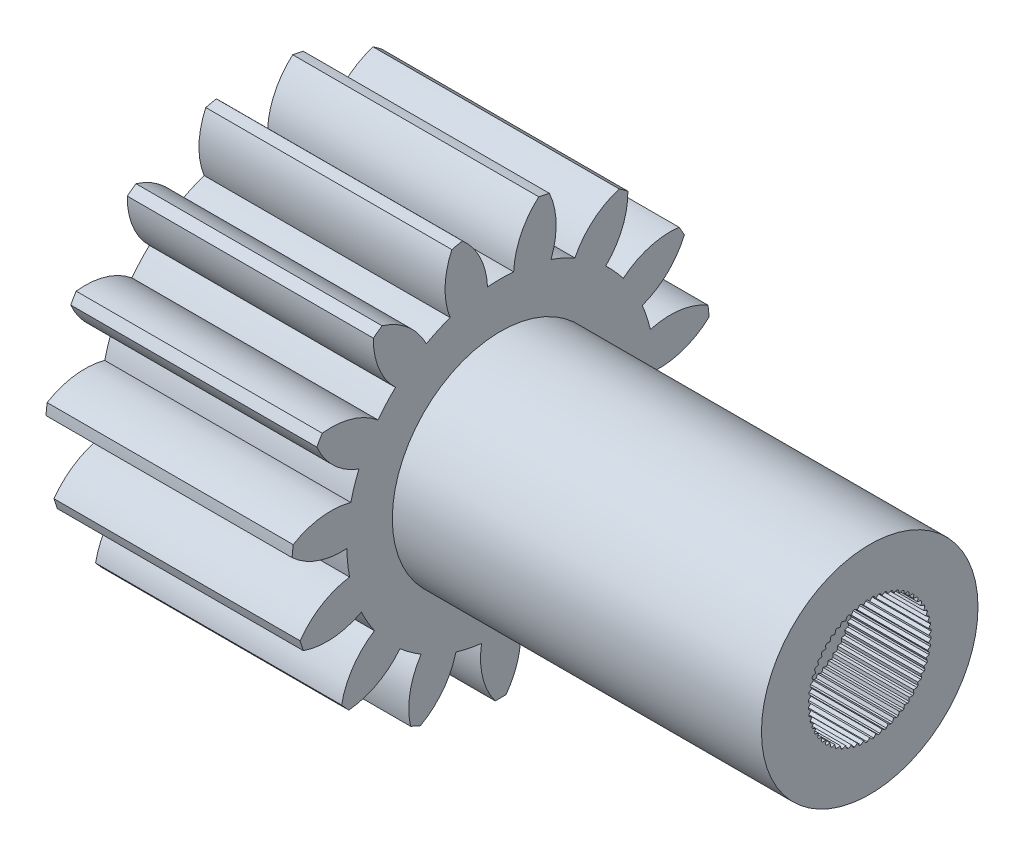
SolidWorks part; units mm, degrees
ref_plane "Plane1" through (0, 0, 0) normal (0, 0, 1) x (1, 0, 0)
ref_plane "Plane2" through (0, 0, 0) normal (0, 1, 0) x (1, 0, 0)
ref_plane "Plane3" through (0, 0, 0) normal (1, 0, 0) x (0, 0, -1)
sketch "HoldingSke" plane through (0, 0, 0) normal (0, 1, 0) x (1, 0, 0)
  line L0 (0, 0) -> (0.9659, -0.2588)
  line L1 (-15, 0) -> (100, 0) construction
  line L2 (0, 0) -> (-2.1039, 2.3779)
  line L3 (0, 0) -> (-11.863, 4.5341)
  line L4 (0, 0) -> (8.3417, 2.2352)
  line L5 (0, 0) -> (-46.8476, -17.4728)
  line L6 (0, 0) -> (-8.2896, -5.593)
  line L7 (-2.1039, 2.3779) -> (8.6586, 51.2059)
  line L8 (-76.2, 54.61) -> (-75.3, 54.61)
  line L9 (-71.009, 38.7566) -> (-53.1078, 45.2721)
  line L10 (-76.2, 71.12) -> (104.1128, 71.12)
  line L11 (0, 0) -> (-10, 0)
  line L12 (-76.2, 101.6) -> (-76.162, 101.6)
  line L13 (24.9733, 27.94) -> (52.9518, 28.4284)
  line L14 (24.9733, 27.94) -> (24.9743, 27.94)
  line L15 (24.9733, 27.94) -> (100.4006, 29.5858)
  line L16 (-63.627, -1) -> (-12.827, -1)
  circle A0 centre (0, 0) radius 2.5
  circle A1 centre (0, 0) radius 6.249
  circle A2 centre (0, 0) radius 37.5
  circle A3 centre (0, 0) radius 2.5
  dimension "Num_teeth" = 15
  dimension "Pitch_radius" = 180.3128
  dimension "Width" = 10
  dimension "Thickness" = 10
sketch "BasProSke" plane through (0, 0, 0) normal (0, 1, 0) x (1, 0, 0)
  line L0 (-10, 0) -> (60, 0) construction
  line L1 (0, 0) -> (0, 8.5)
  line L2 (0, 0) -> (10, 0)
  line L3 (10, 0) -> (10, 8.5)
  line L4 (10, 8.5) -> (0, 8.5)
  dimension "Thickness" = 10
  dimension "Diameter" = 17
revolve "Base-Revolve" add sketch "BasProSke" angle 360 about L0
sketch "TooCutSke" plane through (0, 0, 0) normal (1, 0, 0) x (0, 0, -1)
  line L1 (0, 0) -> (0, 107) construction
  line L2 (0, 0) -> (-0.8504, 7.4516) construction
  line L3 (0, 0) -> (-3.1044, 14.6049) construction
  line L4 (-0.8504, 7.4516) -> (-1.5522, 7.3025) construction
  arc A0 (0.5316, 6.2263) -> (-0.5316, 6.2263) centre (0, 0) ccw
  arc A1 (1.5766, 8.3784) -> (-1.5766, 8.3784) centre (0, 0) ccw
  circle A2 centre (0, 0) radius 7.5 construction
  circle A3 centre (0, 0) radius 7.0477 construction
  arc A4 (-0.5316, 6.2263) -> (-1.5766, 8.3784) centre (-3.5289, 6.1005) ccw
  arc A5 (1.5766, 8.3784) -> (0.5316, 6.2263) centre (3.5289, 6.1005) ccw
extrude "ToothCut" cut sketch "TooCutSke" along normal through all
fillet "Breaks" [suppressed] radius 0.02 tangent propagation no
fillet "RootFillets" [suppressed] radius 0.251
pattern_circular "TeethCuts" count 15 every 24 about axis through (-10, 0, 0) along (1, 0, 0) of "ToothCut", "RootFillets", "Breaks"
sketch "HubNeaOneSke" plane through (0, 0, 0) normal (-1, 0, 0) x (0, 0, 1)
  circle A0 centre (0, 0) radius 6.249
  dimension "Diameter" = 12.498
extrude "HubNearOne" [suppressed] add sketch "HubNeaOneSke" along normal blind 40.0001
sketch "HubNeaBotSke" plane through (0, 0, 0) normal (-1, 0, 0) x (0, 0, 1)
  circle A0 centre (0, 0) radius 6.249
  dimension "Diameter" = 12.498
extrude "HubNearBoth" [suppressed] add sketch "HubNeaBotSke" along normal blind 20
ref_plane "FarPln" through (10, 0, 0) normal (1, 0, 0) x (0, 0, -1)
sketch "HubFarSke" plane through (10, 0, 0) normal (1, 0, 0) x (0, 0, -1)
  circle A0 centre (0, 0) radius 6.249
  dimension "Diameter" = 12.498
extrude "HubFar" [suppressed] add sketch "HubFarSke" along normal blind 20
sketch "BorSke" plane through (0, 0, 0) normal (1, 0, 0) x (0, 0, -1)
  circle A0 centre (0, 0) radius 2.5
  dimension "Diameter" = 5
extrude "Bore" cut sketch "BorSke" along normal mid plane 100.0001
sketch "KeySke" plane through (0, 0, 0) normal (1, 0, 0) x (0, 0, -1)
  line L0 (-1, 0) -> (-1, 3.4)
  line L1 (-1, 3.4) -> (1, 3.4)
  line L2 (1, 3.4) -> (1, 0)
  line L3 (0, 0) -> (0, 34) construction
  line L4 (-1, 0) -> (1, 0)
  dimension "Width" = 2
extrude "Keyway" [suppressed] cut sketch "KeySke" along normal mid plane 100.0001
pattern_circular "Keyway2" [suppressed] count 2 every 90 about axis through (-10, 0, 0) along (1, 0, 0)
sketch "Sketch1" plane through (10, 0, 0) normal (1, 0, 0) x (0, 0, -1)
  circle A1 centre (0, 0) radius 2.5
  circle A2 centre (0, 0) radius 4.4
  circle A3 centre (0, 0) radius 4.4
  arc A60 (-8.4736, 0.67) -> (-6.2478, -0.1222) centre (-6.436, 2.8719) ccw
  arc A61 (-6.2478, -0.1222) -> (-6.1367, -1.1795) centre (0, 0) ccw
  arc A62 (-6.1367, -1.1795) -> (-8.1491, -2.4171) centre (-5.6982, -4.1473) ccw
  arc A63 (-8.1491, -2.4171) -> (-8.0135, -2.8344) centre (0, 0) ccw
  arc A64 (-8.0135, -2.8344) -> (-5.658, -2.6528) centre (-7.0477, 0.0059) ccw
  arc A65 (-5.658, -2.6528) -> (-5.1264, -3.5735) centre (0, 0) ccw
  arc A66 (-5.1264, -3.5735) -> (-6.4614, -5.5227) centre (-3.5188, -6.1064) ccw
  arc A67 (-6.4614, -5.5227) -> (-6.1678, -5.8487) centre (0, 0) ccw
  arc A68 (-6.1678, -5.8487) -> (-4.0898, -4.7248) centre (-6.4408, -2.8612) ccw
  arc A69 (-4.0898, -4.7248) -> (-3.2297, -5.3497) centre (0, 0) ccw
  arc A70 (-3.2297, -5.3497) -> (-3.6565, -7.6733) centre (-0.7308, -7.0097) ccw
  arc A71 (-3.6565, -7.6733) -> (-3.2557, -7.8518) centre (0, 0) ccw
  arc A72 (-3.2557, -7.8518) -> (-1.8145, -5.9798) centre (-4.7202, -5.2335) ccw
  arc A73 (-1.8145, -5.9798) -> (-0.7746, -6.2008) centre (0, 0) ccw
  arc A74 (-0.7746, -6.2008) -> (-0.2194, -8.4972) centre (2.1834, -6.7009) ccw
  arc A75 (-0.2194, -8.4972) -> (0.2194, -8.4972) centre (0, 0) ccw
  arc A76 (0.2194, -8.4972) -> (0.7746, -6.2008) centre (-2.1834, -6.7009) ccw
  arc A77 (0.7746, -6.2008) -> (1.8145, -5.9798) centre (0, 0) ccw
  arc A78 (1.8145, -5.9798) -> (3.2557, -7.8518) centre (4.7202, -5.2335) ccw
  arc A79 (3.2557, -7.8518) -> (3.6565, -7.6733) centre (0, 0) ccw
  arc A80 (3.6565, -7.6733) -> (3.2297, -5.3497) centre (0.7308, -7.0097) ccw
  arc A81 (3.2297, -5.3497) -> (4.0898, -4.7248) centre (0, 0) ccw
  arc A82 (4.0898, -4.7248) -> (6.1678, -5.8487) centre (6.4408, -2.8612) ccw
  arc A83 (6.1678, -5.8487) -> (6.4614, -5.5227) centre (0, 0) ccw
  arc A84 (6.4614, -5.5227) -> (5.1264, -3.5735) centre (3.5188, -6.1064) ccw
  arc A85 (5.1264, -3.5735) -> (5.658, -2.6528) centre (0, 0) ccw
  arc A86 (5.658, -2.6528) -> (8.0135, -2.8344) centre (7.0477, 0.0059) ccw
  arc A87 (8.0135, -2.8344) -> (8.1491, -2.4171) centre (0, 0) ccw
  arc A88 (8.1491, -2.4171) -> (6.1367, -1.1795) centre (5.6982, -4.1473) ccw
  arc A89 (6.1367, -1.1795) -> (6.2478, -0.1222) centre (0, 0) ccw
  arc A90 (6.2478, -0.1222) -> (8.4736, 0.67) centre (6.436, 2.8719) ccw
  arc A91 (8.4736, 0.67) -> (8.4277, 1.1064) centre (0, 0) ccw
  arc A92 (8.4277, 1.1064) -> (6.0859, 1.4185) centre (6.8925, -1.471) ccw
  arc A93 (6.0859, 1.4185) -> (5.7573, 2.4296) centre (0, 0) ccw
  arc A94 (5.7573, 2.4296) -> (7.4685, 4.0586) centre (4.7115, 5.2414) ccw
  arc A95 (7.4685, 4.0586) -> (7.2491, 4.4386) centre (0, 0) ccw
  arc A96 (7.2491, 4.4386) -> (4.9828, 3.7712) centre (6.8949, 1.4595) ccw
  arc A97 (4.9828, 3.7712) -> (4.2714, 4.5613) centre (0, 0) ccw
  arc A98 (4.2714, 4.5613) -> (5.172, 6.7454) centre (2.1723, 6.7046) ccw
  arc A99 (5.172, 6.7454) -> (4.817, 7.0033) centre (0, 0) ccw
  arc A100 (4.817, 7.0033) -> (3.0181, 5.4718) centre (5.7052, 4.1378) ccw
  arc A101 (3.0181, 5.4718) -> (2.0469, 5.9043) centre (0, 0) ccw
  arc A102 (2.0469, 5.9043) -> (1.9812, 8.2659) centre (-0.7425, 7.0085) ccw
  arc A103 (1.9812, 8.2659) -> (1.5521, 8.3571) centre (0, 0) ccw
  arc A104 (1.5521, 8.3571) -> (0.5316, 6.2263) centre (3.5289, 6.1005) ccw
  arc A105 (0.5316, 6.2263) -> (-0.5316, 6.2263) centre (0, 0) ccw
  arc A106 (-0.5316, 6.2263) -> (-1.5521, 8.3571) centre (-3.5289, 6.1005) ccw
  arc A107 (-1.5521, 8.3571) -> (-1.9812, 8.2659) centre (0, 0) ccw
  arc A108 (-1.9812, 8.2659) -> (-2.0469, 5.9043) centre (0.7425, 7.0085) ccw
  arc A109 (-2.0469, 5.9043) -> (-3.0181, 5.4718) centre (0, 0) ccw
  arc A110 (-3.0181, 5.4718) -> (-4.817, 7.0033) centre (-5.7052, 4.1378) ccw
  arc A111 (-4.817, 7.0033) -> (-5.172, 6.7454) centre (0, 0) ccw
  arc A112 (-5.172, 6.7454) -> (-4.2714, 4.5613) centre (-2.1723, 6.7046) ccw
  arc A113 (-4.2714, 4.5613) -> (-4.9828, 3.7712) centre (0, 0) ccw
  arc A114 (-4.9828, 3.7712) -> (-7.2491, 4.4386) centre (-6.8949, 1.4595) ccw
  arc A115 (-7.2491, 4.4386) -> (-7.4685, 4.0586) centre (0, 0) ccw
  arc A116 (-7.4685, 4.0586) -> (-5.7573, 2.4296) centre (-4.7115, 5.2414) ccw
  arc A117 (-5.7573, 2.4296) -> (-6.0859, 1.4185) centre (0, 0) ccw
  arc A118 (-6.0859, 1.4185) -> (-8.4277, 1.1064) centre (-6.8925, -1.471) ccw
  arc A119 (-8.4277, 1.1064) -> (-8.4736, 0.67) centre (0, 0) ccw
  arc A120 (-8.4736, 0.67) -> (-6.2478, -0.1222) centre (-6.436, 2.8719) ccw
  arc A121 (-6.2478, -0.1222) -> (-6.1367, -1.1795) centre (0, 0) ccw
  arc A122 (-6.1367, -1.1795) -> (-8.1491, -2.4171) centre (-5.6982, -4.1473) ccw
  arc A123 (-8.1491, -2.4171) -> (-8.0135, -2.8344) centre (0, 0) ccw
  arc A124 (-8.0135, -2.8344) -> (-5.658, -2.6528) centre (-7.0477, 0.0059) ccw
  arc A125 (-5.658, -2.6528) -> (-5.1264, -3.5735) centre (0, 0) ccw
  arc A126 (-5.1264, -3.5735) -> (-6.4614, -5.5227) centre (-3.5188, -6.1064) ccw
  arc A127 (-6.4614, -5.5227) -> (-6.1678, -5.8487) centre (0, 0) ccw
  arc A128 (-6.1678, -5.8487) -> (-4.0898, -4.7248) centre (-6.4408, -2.8612) ccw
  arc A129 (-4.0898, -4.7248) -> (-3.2297, -5.3497) centre (0, 0) ccw
  arc A130 (-3.2297, -5.3497) -> (-3.6565, -7.6733) centre (-0.7308, -7.0097) ccw
  arc A131 (-3.6565, -7.6733) -> (-3.2557, -7.8518) centre (0, 0) ccw
  arc A132 (-3.2557, -7.8518) -> (-1.8145, -5.9798) centre (-4.7202, -5.2335) ccw
  arc A133 (-1.8145, -5.9798) -> (-0.7746, -6.2008) centre (0, 0) ccw
  arc A134 (-0.7746, -6.2008) -> (-0.2194, -8.4972) centre (2.1834, -6.7009) ccw
  arc A135 (-0.2194, -8.4972) -> (0.2194, -8.4972) centre (0, 0) ccw
  arc A136 (0.2194, -8.4972) -> (0.7746, -6.2008) centre (-2.1834, -6.7009) ccw
  arc A137 (0.7746, -6.2008) -> (1.8145, -5.9798) centre (0, 0) ccw
  arc A138 (1.8145, -5.9798) -> (3.2557, -7.8518) centre (4.7202, -5.2335) ccw
  arc A139 (3.2557, -7.8518) -> (3.6565, -7.6733) centre (0, 0) ccw
  arc A140 (3.6565, -7.6733) -> (3.2297, -5.3497) centre (0.7308, -7.0097) ccw
  arc A141 (3.2297, -5.3497) -> (4.0898, -4.7248) centre (0, 0) ccw
  arc A142 (4.0898, -4.7248) -> (6.1678, -5.8487) centre (6.4408, -2.8612) ccw
  arc A143 (6.1678, -5.8487) -> (6.4614, -5.5227) centre (0, 0) ccw
  arc A144 (6.4614, -5.5227) -> (5.1264, -3.5735) centre (3.5188, -6.1064) ccw
  arc A145 (5.1264, -3.5735) -> (5.658, -2.6528) centre (0, 0) ccw
  arc A146 (5.658, -2.6528) -> (8.0135, -2.8344) centre (7.0477, 0.0059) ccw
  arc A147 (8.0135, -2.8344) -> (8.1491, -2.4171) centre (0, 0) ccw
  arc A148 (8.1491, -2.4171) -> (6.1367, -1.1795) centre (5.6982, -4.1473) ccw
  arc A149 (6.1367, -1.1795) -> (6.2478, -0.1222) centre (0, 0) ccw
  arc A150 (6.2478, -0.1222) -> (8.4736, 0.67) centre (6.436, 2.8719) ccw
  arc A151 (8.4736, 0.67) -> (8.4277, 1.1064) centre (0, 0) ccw
  arc A152 (8.4277, 1.1064) -> (6.0859, 1.4185) centre (6.8925, -1.471) ccw
  arc A153 (6.0859, 1.4185) -> (5.7573, 2.4296) centre (0, 0) ccw
  arc A154 (5.7573, 2.4296) -> (7.4685, 4.0586) centre (4.7115, 5.2414) ccw
  arc A155 (7.4685, 4.0586) -> (7.2491, 4.4386) centre (0, 0) ccw
  arc A156 (7.2491, 4.4386) -> (4.9828, 3.7712) centre (6.8949, 1.4595) ccw
  arc A157 (4.9828, 3.7712) -> (4.2714, 4.5613) centre (0, 0) ccw
  arc A158 (4.2714, 4.5613) -> (5.172, 6.7454) centre (2.1723, 6.7046) ccw
  arc A159 (5.172, 6.7454) -> (4.817, 7.0033) centre (0, 0) ccw
  arc A160 (4.817, 7.0033) -> (3.0181, 5.4718) centre (5.7052, 4.1378) ccw
  arc A161 (3.0181, 5.4718) -> (2.0469, 5.9043) centre (0, 0) ccw
  arc A162 (2.0469, 5.9043) -> (1.9812, 8.2659) centre (-0.7425, 7.0085) ccw
  arc A163 (1.9812, 8.2659) -> (1.5521, 8.3571) centre (0, 0) ccw
  arc A164 (1.5521, 8.3571) -> (0.5316, 6.2263) centre (3.5289, 6.1005) ccw
  arc A165 (0.5316, 6.2263) -> (-0.5316, 6.2263) centre (0, 0) ccw
  arc A166 (-0.5316, 6.2263) -> (-1.5521, 8.3571) centre (-3.5289, 6.1005) ccw
  arc A167 (-1.5521, 8.3571) -> (-1.9812, 8.2659) centre (0, 0) ccw
  arc A168 (-1.9812, 8.2659) -> (-2.0469, 5.9043) centre (0.7425, 7.0085) ccw
  arc A169 (-2.0469, 5.9043) -> (-3.0181, 5.4718) centre (0, 0) ccw
  arc A170 (-3.0181, 5.4718) -> (-4.817, 7.0033) centre (-5.7052, 4.1378) ccw
  arc A171 (-4.817, 7.0033) -> (-5.172, 6.7454) centre (0, 0) ccw
  arc A172 (-5.172, 6.7454) -> (-4.2714, 4.5613) centre (-2.1723, 6.7046) ccw
  arc A173 (-4.2714, 4.5613) -> (-4.9828, 3.7712) centre (0, 0) ccw
  arc A174 (-4.9828, 3.7712) -> (-7.2491, 4.4386) centre (-6.8949, 1.4595) ccw
  arc A175 (-7.2491, 4.4386) -> (-7.4685, 4.0586) centre (0, 0) ccw
  arc A176 (-7.4685, 4.0586) -> (-5.7573, 2.4296) centre (-4.7115, 5.2414) ccw
  arc A177 (-5.7573, 2.4296) -> (-6.0859, 1.4185) centre (0, 0) ccw
  arc A178 (-6.0859, 1.4185) -> (-8.4277, 1.1064) centre (-6.8925, -1.471) ccw
  arc A179 (-8.4277, 1.1064) -> (-8.4736, 0.67) centre (0, 0) ccw
  dimension "D1" = 0
  dimension "D2" = 1.9
extrude "Boss-Extrude1" add sketch "Sketch1" along normal blind 15 contours A3 A1 region at (10, 0, 4.2755)
sketch "Sketch2" plane through (25, 0, 0) normal (1, 0, 0) x (0, 0, -1)
  line L0 (0, 10.8289) -> (0, -5.5545) construction
  line L1 (0, 2.4) -> (-0.2372, 2.6372)
  line L2 (0, 2.4) -> (0.2372, 2.6372)
  line L3 (-0.2372, 2.6372) -> (0.2372, 2.6372)
  circle A0 centre (0, 0) radius 2.5
  point P7 (0, 2.6372)
  circle M5 centre (0, 0) radius 2.5
  dimension "D1" = 5
  dimension "D3" = 0.1
  dimension "D2" = 90
  dimension "D4" = 0.4743
extrude "Boss-Extrude2" add sketch "Sketch2" against normal blind 3.1 contours L0 L1 M5 | A0 L0 L2 region at (25, 2.4662, -0.0328) region at (25, 2.4662, 0.0328)
ref_axis "Axis1" through (25, 0, 0) along (-1, 0, 0)
pattern_circular "CirPattern1" count 60 over 360 about axis through (25, 0, 0) along (-1, 0, 0) of "Boss-Extrude2"
ref_plane "Plane4" through (21.9, 0, 0) normal (1, 0, 0) x (0, 0, -1)
sketch "Sketch4" plane through (21.9, 0, 0) normal (1, 0, 0) x (0, 0, -1)
  circle A0 centre (0, 0) radius 2.5
  circle A1 centre (0, 0) radius 0.85
  dimension "D1" = 5
  dimension "D2" = 1.7
extrude "Boss-Extrude3" add sketch "Sketch4" against normal blind 0.5
sketch "Sketch5" plane through (0, 0, 0) normal (-1, 0, 0) x (0, 0, 1)
  circle A0 centre (0, 0) radius 3.5
  dimension "D1" = 7
extrude "Cut-Extrude1" cut sketch "Sketch5" against normal blind 21
equation "' \"Module@HoldingSke\" = 6.35"
equation "' \"Num_teeth@HoldingSke\" = 12"
equation "' \"Ap@HoldingSke\" =  20"
equation "' \"Ap@HoldingSke\" = 20"
equation "' \"Width@HoldingSke\" = 0.5 * 25.4"
equation "' \"Hub_dia@HoldingSke\"= 1 * 25.4"
equation "' \"Hub_dia@HoldingSke\" = 1 * 25.4"
equation "' \"Overall_len@HoldingSke\" = 1.0 * 25.4"
equation "' \"Bore@HoldingSke\" = 0.75 * 25.4"
equation "' \"T_dim@HoldingSke\" = 0.1 * 25.4"
equation "' \"Width@KeySke\" = 0.25 * 25.4"
equation "' \"Show_teeth@HoldingSke\" = 13"
equation "' \"Backlash@HoldingSke\" = 0.009 * 25.4"
equation "' \"Addendum_fac@HoldingSke\" = 1.0"
equation "' \"Dedendum_fac@HoldingSke\" = 1.25"
equation "' \"Dedendum_add@HoldingSke\" = 0.00005 * 25.4"
equation "' \"Clearance_fac@HoldingSke\" = 0.25"
equation "\"Pitch@HoldingSke\" = 1 / \"Module@HoldingSke\""
equation "\"Overcut_dia@TooCutSke\" = (\"Num_teeth@HoldingSke\" + 2 * \"Addendum_fac@HoldingSke\") / \"Pitch@HoldingSke\" + 0.002 * 25.4"
equation "\"Pitch_dia@TooCutSke\" = \"Num_teeth@HoldingSke\" / \"Pitch@HoldingSke\""
equation "\"Base_dia@TooCutSke\" = \"Num_teeth@HoldingSke\" / \"Pitch@HoldingSke\" * cos((\"Ap@HoldingSke\"  * 3.14159265 / 180))"
equation "\"Root_dia@TooCutSke\" = (\"Num_teeth@HoldingSke\" + 2) / \"Pitch@HoldingSke\" - 2 * (\"Addendum_fac@HoldingSke\" + \"Dedendum_fac@HoldingSke\") / \"Pitch@HoldingSke\" - \"Dedendum_add@HoldingSke\" * 2"
equation "\"Half_ang@TooCutSke\" = 180 / \"Num_teeth@HoldingSke\""
equation "\"Half_CT@TooCutSke\" = \"Num_teeth@HoldingSke\" / \"Pitch@HoldingSke\" * sin((3.14159265 / 2 / \"Num_teeth@HoldingSke\")) / 2 - 7 * \"Backlash@HoldingSke\" / 4"
equation "\"Flank_rad@TooCutSke\" = \"Num_teeth@HoldingSke\" / \"Pitch@HoldingSke\" / 5"
equation "\"Radius@RootFillets\" = \"Clearance_fac@HoldingSke\" / \"Pitch@HoldingSke\" + \"Dedendum_add@HoldingSke\""
equation "\"Break_rad@Breaks\" = 0.02 / \"Pitch@HoldingSke\""
equation "\"Thickness@HoldingSke\" = \"Width@HoldingSke\""
equation "\"OAL@HoldingSke\" = \"Thickness@HoldingSke\""
equation "\"MHD@HoldingSke\" = (\"Num_teeth@HoldingSke\" + 2) / \"Pitch@HoldingSke\" - 2 * (\"Addendum_fac@HoldingSke\" + \"Dedendum_fac@HoldingSke\")  / \"Pitch@HoldingSke\" - \"Dedendum_add@HoldingSke\" * 2"
equation "\"MBD@HoldingSke\" = (\"Num_teeth@HoldingSke\" + 2) / \"Pitch@HoldingSke\" - 2 * (\"Addendum_fac@HoldingSke\" + \"Dedendum_fac@HoldingSke\")  / \"Pitch@HoldingSke\" - \"Dedendum_add@HoldingSke\" * 2 - 0.002 * 25.4"
equation "\"MHD@HoldingSke\" = ((sgn( \"MHD@HoldingSke\" - \"Hub_dia@HoldingSke\" )-1)*( \"MHD@HoldingSke\" - \"Hub_dia@HoldingSke\" ))/-2+ \"Hub_dia@HoldingSke\""
equation "\"MBD@HoldingSke\" = ((sgn( \"MBD@HoldingSke\" - \"Bore@HoldingSke\" )-1)*( \"MBD@HoldingSke\" - \"Bore@HoldingSke\" ))/-2+ \"Bore@HoldingSke\""
equation "\"OAL@HoldingSke\" = ((sgn( \"OAL@HoldingSke\" - \"Overall_len@HoldingSke\" )+1)*( \"OAL@HoldingSke\" - \"Overall_len@HoldingSke\" ))/2 + \"Overall_len@HoldingSke\" + 0.000002 * 25.4"
equation "\"Num_teeth@TeethCuts\" = int( \"Show_teeth@HoldingSke\" ) + 1"
equation "\"Num_teeth@TeethCuts\" = ((sgn( \"Num_teeth@TeethCuts\" - \"Num_teeth@HoldingSke\" )-1)*( \"Num_teeth@TeethCuts\" - \"Num_teeth@HoldingSke\" ))/-2+ \"Num_teeth@HoldingSke\""
equation "\"Num_teeth@TeethCuts\" = ((sgn( \"Num_teeth@TeethCuts\" - 2.0)+1)*( \"Num_teeth@TeethCuts\" - 2.0))/2 +2.0"
equation "\"Angle@TeethCuts\" = 360.0 / \"Num_teeth@HoldingSke\""
equation "\"Diameter@BasProSke\" = (\"Num_teeth@HoldingSke\" + 2 * \"Addendum_fac@HoldingSke\") / \"Pitch@HoldingSke\""
equation "\"Thickness@BasProSke\"  = \"Thickness@HoldingSke\""
equation "' \"Fillet_rad@BasProSke\" =  \"Thickness@HoldingSke\" * 0.05"
equation "' \"Fillet_rad@BasProSke\" = \"Thickness@HoldingSke\" * 0.05"
equation "\"MHD@HoldingSke\" = ((sgn( \"MHD@HoldingSke\" - \"Root_dia@TooCutSke\" )-1)*( \"MHD@HoldingSke\" - \"Root_dia@TooCutSke\" ))/-2+ \"Root_dia@TooCutSke\""
equation "\"Diameter@HubNeaOneSke\" = \"MHD@HoldingSke\""
equation "\"Length@HubNearOne\" = \"OAL@HoldingSke\" - \"Thickness@BasProSke\""
equation "\"Diameter@HubNeaBotSke\" = \"MHD@HoldingSke\""
equation "\"Length@HubNearBoth\" = ( \"OAL@HoldingSke\" - \"Thickness@BasProSke\" ) / 2.0"
equation "\"Thickness@FarPln\" = \"Thickness@BasProSke\""
equation "\"Diameter@HubFarSke\" = \"MHD@HoldingSke\""
equation "\"Length@HubFar\" = ( \"OAL@HoldingSke\" - \"Thickness@BasProSke\" ) / 2.0"
equation "\"Diameter@BorSke\" = \"MBD@HoldingSke\""
equation "\"D1@Bore\" = \"OAL@HoldingSke\" * 2.0"
equation "\"D1@Keyway\" = \"OAL@HoldingSke\" * 2.0"
equation "\"Offset@KeySke\" = \"T_dim@HoldingSke\" + \"MBD@HoldingSke\" / 2.0"
